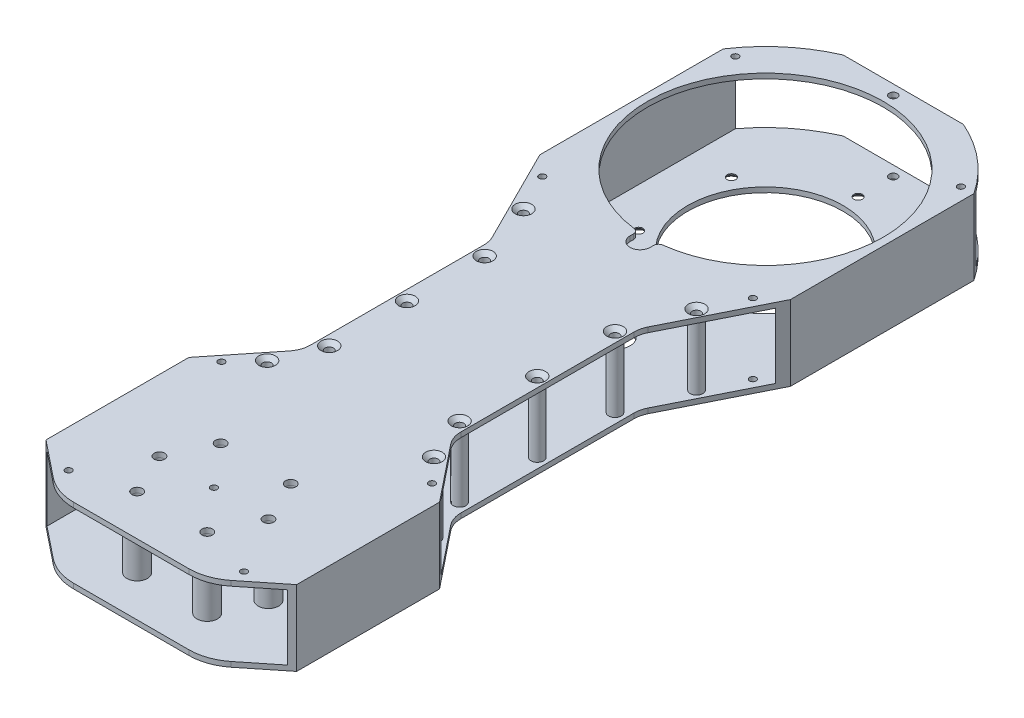
SolidWorks part; units mm, degrees
material "6061-T4 (SS)"
ref_plane "前视基准面" through (0, 0, 0) normal (0, 0, 1) x (1, 0, 0)
ref_plane "上视基准面" through (0, 0, 0) normal (0, 1, 0) x (1, 0, 0)
ref_plane "右视基准面" through (0, 0, 0) normal (1, 0, 0) x (0, 0, -1)
sketch "草图1" plane through (0, 0, 0) normal (0, 0, 1) x (1, 0, 0)
  line L0 (-48, 13) -> (-48, -13)
  line L1 (-50, 15) -> (50, 15)
  line L2 (-50, 15) -> (-50, -15)
  line L3 (-50, -15) -> (50, -15)
  line L4 (50, 15) -> (50, -15)
  line L5 (-50, 15) -> (50, -15) construction
  line L6 (-50, -15) -> (50, 15) construction
  line L7 (-48, -13) -> (48, -13)
  line L8 (48, 13) -> (48, -13)
  line L9 (-48, 13) -> (48, 13)
  point P0 (0, 0)
  dimension "D1" = 100
  dimension "D2" = 30
  dimension "D3" = 2
extrude "凸台-拉伸1" add sketch "草图1" along normal blind 315
sketch "草图2" plane through (0, -15, 0) normal (0, -1, 0) x (1, 0, 0)
  line L1 (-50, 315) -> (50, 315) construction
  circle A0 centre (0, 275) radius 5
  point P5 (0, 315)
  dimension "D1" = 10
  dimension "D2" = 40
extrude "切除-拉伸1" cut sketch "草图2" against normal up to next
sketch "草图3" plane through (0, 15, 0) normal (0, 1, 0) x (1, 0, 0)
  line L0 (50, 0) -> (-50, 0) construction
  circle A0 centre (0, -55) radius 47
  dimension "D1" = 94
  dimension "D2" = 8
extrude "切除-拉伸2" cut sketch "草图3" against normal up to next
sketch "草图8" plane through (0, -15, 0) normal (0, -1, 0) x (1, 0, 0)
  line L0 (0, 275) -> (-18.5467, 297.1031) construction
  line L1 (0, -16.5) -> (0, 16.5) construction
  line L2 (0, 275) -> (18.5467, 297.1031) construction
  line L3 (0, 275) -> (14.5634, 275) construction
  circle A0 centre (0, 275) radius 21.75 construction
  circle A1 centre (-13.9806, 291.6615) radius 2.1
  circle A2 centre (13.9806, 291.6615) radius 2.1
  circle A3 centre (13.9806, 258.3385) radius 2.1
  circle A4 centre (-13.9806, 258.3385) radius 2.1
  circle A5 centre (-21.75, 275) radius 2.1
  circle A6 centre (21.75, 275) radius 2.1
  dimension "D1" = 43.5
  dimension "D3" = 4.2
  dimension "D2" = 80
extrude "切除-拉伸7" cut sketch "草图8" against normal through all
sketch "草图9" plane through (0, -15, 0) normal (0, -1, 0) x (1, 0, 0)
  circle A0 centre (0, 55) radius 37 construction
  circle A1 centre (0, 55) radius 47 construction
  circle A2 centre (-32.0429, 73.5) radius 1.6
  circle A3 centre (0, 92) radius 1.6
  circle A4 centre (32.0429, 73.5) radius 1.6
  circle A5 centre (32.0429, 36.5) radius 1.6
  circle A6 centre (0, 18) radius 1.6
  circle A7 centre (-32.0429, 36.5) radius 1.6
  point P18 (0, 55)
  dimension "D1" = 74
  dimension "D2" = 3.2
  dimension "D3" = 6
extrude "切除-拉伸8" cut sketch "草图9" against normal up to next
sketch "草图5" plane through (0, 15, 0) normal (0, 1, 0) x (1, 0, 0)
  line L0 (-50, -95) -> (-30, -135)
  line L1 (-50, -315) -> (-50, 0) construction
  line L2 (-30, -135) -> (-30, -210)
  line L3 (-30, -210) -> (-50, -235)
  line L4 (-50, -95) -> (-50, -235)
  line L5 (0, -16.5) -> (0, 16.5) construction
  line L6 (50, -95) -> (50, -235)
  line L7 (30, -210) -> (50, -235)
  line L8 (30, -135) -> (30, -210)
  line L9 (50, -95) -> (30, -135)
  line L10 (50, 0) -> (-50, 0) construction
  line L11 (50, -315) -> (-50, -315) construction
  dimension "D1" = 20
  dimension "D2" = 25
  dimension "D3" = 40
  dimension "D4" = 95
  dimension "D5" = 80
extrude "切除-拉伸4" cut sketch "草图5" against normal through all
sketch "草图6" plane through (0, 15, 0) normal (0, 1, 0) x (1, 0, 0)
  line L1 (-23.9792, 0) -> (-50, 0)
  line L3 (-50, -95) -> (-50, 0) construction
  line L9 (50, 0) -> (-50, 0) construction
  line L10 (50, 0) -> (23.9792, 0)
  line L13 (50, -95) -> (50, 0) construction
  line L14 (50, -95) -> (50, -88.9217)
  line L15 (-50, -21.8338) -> (-50, 0)
  line L16 (50, -21.8338) -> (50, 0)
  arc A0 (50, -21.8338) -> (23.9792, 0) centre (0, -55) ccw
  arc A1 (-23.9792, 0) -> (-50, -21.8338) centre (0, -55) ccw
  line M11 (-50, 0) -> (-50, -95)
  line M23 (50, -95) -> (50, 0)
  line M24 (50, 0) -> (-50, 0)
  dimension "D1" = 60
extrude "切除-拉伸5" cut sketch "草图6" against normal through all contours A1 M24 M11 | A0 M23 M24 region at (-42.232, 15, 6.5725) region at (42.232, 15, 6.5725)
fillet "圆角1" radius 10 8 edges at (-30, 14, 210) (-30, -14, 210) (-30, -14, 135) (-30, 14, 135) (30, 14, 210) (30, -14, 210) (30, 14, 135) (30, -14, 135)
sketch "草图10" plane through (0, 15, 0) normal (0, 1, 0) x (1, 0, 0)
  line L0 (-30, -206.4922) -> (-30, -137.3607) construction
  line L1 (0, -16.5) -> (0, 16.5) construction
  line L2 (-26, -141) -> (-26, -203) construction
  line L3 (-31.0557, -132.8885) -> (-50, -95) construction
  line L4 (-50, -235) -> (-32.1913, -212.7391) construction
  circle A0 centre (-26, -141) radius 1.6
  circle A1 centre (0, -55) radius 47 construction
  circle A2 centre (-26, -203) radius 1.6
  circle A3 centre (0, -275) radius 5 construction
  circle A4 centre (26, -203) radius 1.6
  circle A5 centre (26, -141) radius 1.6
  circle A6 centre (-26, -172) radius 1.6
  circle A7 centre (26, -172) radius 1.6
  circle A8 centre (-34.5279, -117) radius 1.6
  circle A9 centre (-33.2775, -220.5) radius 1.6
  circle A10 centre (33.2775, -220.5) radius 1.6
  circle A11 centre (34.5279, -117) radius 1.6
  dimension "D1" = 3.2
  dimension "D4" = 72
  dimension "D5" = 4
  dimension "D2" = 4
  dimension "D3" = 86
  dimension "D6" = 18
  dimension "D7" = 4
  dimension "D8" = 12
extrude "切除-拉伸9" cut sketch "草图10" against normal through all
sketch "草图11" plane through (0, -13, 0) normal (0, 1, 0) x (1, 0, 0)
  line L0 (0, -16.5) -> (0, 16.5) construction
  circle A0 centre (-26, -141) radius 2.5
  circle A1 centre (-26, -203) radius 2.5
  circle A2 centre (26, -203) radius 2.5
  circle A3 centre (26, -141) radius 2.5
  circle A4 centre (-26, -172) radius 2.5
  circle A5 centre (26, -172) radius 2.5
  circle A6 centre (-33.2775, -220.5) radius 2.5
  circle A7 centre (33.2775, -220.5) radius 2.5
  circle A8 centre (-34.5279, -117) radius 2.5
  circle A9 centre (34.5279, -117) radius 2.5
  dimension "D1" = 5
extrude "凸台-拉伸2" add sketch "草图11" along normal up to surface (26 mm away) up to face at (33.2775, 13, 218.9)
sketch "草图13" plane through (0, -15, 0) normal (0, -1, 0) x (1, 0, 0)
  circle A0 centre (0, 55) radius 31
  circle A2 centre (0, 55) radius 47 construction
  dimension "D1" = 62
extrude "切除-拉伸11" cut sketch "草图13" against normal through all
hole_wizard "M3 十字槽沉头木螺钉的锥形沉头孔1" positions "3D草图1" profile "草图14" countersink size "M3" standard "GB"
sketch3d "3D草图1"
  circle A0 centre (-32.0429, -15, 73.5) radius 1.6 construction
  circle A1 centre (0, -15, 92) radius 1.6 construction
  circle A2 centre (32.0429, -15, 73.5) radius 1.6 construction
  circle A3 centre (32.0429, -15, 36.5) radius 1.6 construction
  circle A4 centre (0, -15, 18) radius 1.6 construction
  circle A5 centre (-32.0429, -15, 36.5) radius 1.6 construction
  point P0 (0, -15, 92)
  point P2 (32.0429, -15, 73.5)
  point P4 (32.0429, -15, 36.5)
  point P6 (0, -15, 18)
  point P8 (-32.0429, -15, 36.5)
  point P10 (-32.0429, -15, 73.5)
  point P15 (-32.0429, -16.6, 73.5)
  point P19 (0, -16.6, 92)
  point P23 (32.0429, -16.6, 73.5)
  point P27 (32.0429, -16.6, 36.5)
  point P31 (0, -16.6, 18)
  point P34 (-32.0429, -16.6, 36.5)
sketch "草图14" plane through (0, -15, 92) normal (1, 0, 0) x (0, 0, -1)
  line L0 (0, 0) -> (0, 8.5215)
  line L1 (0, 8.5215) -> (1.7, 7.5)
  line L2 (1.7, 7.5) -> (1.7, 1.6)
  line L3 (1.7, 1.6) -> (3.3, 0)
  line L5 (3.3, 0) -> (0, 0)
  line L6 (-1.7, 1.6) -> (-3.3, 0) construction
  line L10 (0, 8.5215) -> (-1.7, 7.5) construction
  line L11 (0, -6.35) -> (0, 107.95) construction
  dimension "孔直径" = 3.4
  dimension "孔深度" = 7.5
  dimension "近端锥形沉头孔直径" = 6.6
  dimension "近端锥形沉头孔角度" = 90
  dimension "导头角度" = 118
sketch "草图16" plane through (0, -15, 0) normal (0, -1, 0) x (1, 0, 0)
  line L0 (0, -16.5) -> (0, 16.5) construction
  circle A0 centre (0, 115) radius 6
  circle A1 centre (0, 55) radius 31 construction
  dimension "D1" = 12
  dimension "D2" = 60
extrude "切除-拉伸12" cut sketch "草图16" against normal up to surface (2 mm away) up to face at (0, -13, 93.7)
sketch "草图17" plane through (0, 15, 0) normal (0, 1, 0) x (1, 0, 0)
  line L0 (0, -16.5) -> (0, 16.5) construction
  line L1 (-4, -105) -> (-4, -101.8295)
  line L2 (4, -105) -> (4, -101.8295)
  arc A0 (-4, -105) -> (4, -105) centre (0, -105) ccw
  circle A1 centre (0, -55) radius 47 construction
  arc A2 (-4, -101.8295) -> (4, -101.8295) centre (0, -55) ccw
  dimension "D1" = 50
  dimension "D2" = 8
extrude "切除-拉伸13" cut sketch "草图17" against normal up to surface (2 mm away) up to face at (34.5279, 13, 114.5)
fillet "圆角2" radius 2 2 edges at (4, 14, 101.8295) (-4, 14, 101.8295)
ref_axis "基准轴1" through (0, 0, 0) along (0, 0, -1)
sketch "草图19" plane through (0, 15, 0) normal (0, 1, 0) x (1, 0, 0)
  line L0 (-48, -99) -> (-48, -19) construction
  line L1 (0, -16.5) -> (0, 16.5) construction
  circle A0 centre (-42, -102) radius 1.3
  circle A1 centre (-42, -230) radius 1.3
  circle A2 centre (0, -55) radius 31 construction
  circle A3 centre (42, -230) radius 1.3
  circle A4 centre (42, -102) radius 1.3
  dimension "D1" = 2.6
  dimension "D2" = 6
  dimension "D3" = 47
  dimension "D4" = 128
extrude "切除-拉伸15" cut sketch "草图19" against normal through all
sketch "草图20" plane through (0, 15, 0) normal (0, 1, 0) x (1, 0, 0)
  line L0 (-20.0283, -224.6757) -> (0.0451, -213.62)
  line L1 (-20.0283, -224.6757) -> (-0.0451, -255.7683)
  line L2 (-36.1251, -231.4671) -> (-40.6769, -242.8464)
  line L3 (-40.6769, -242.8464) -> (-38.401, -272.9275)
  line L4 (-38.401, -272.9275) -> (-15.0486, -267.0894)
  line L5 (-15.0486, -267.0894) -> (-36.1251, -231.4671)
  line L6 (0.0081, -277.5729) -> (-13.6536, -285.6561)
  line L7 (-13.6536, -285.6561) -> (-0.0081, -296.1926)
  line L11 (0, -16.5) -> (0, 16.5) construction
  line L12 (13.6536, -285.6561) -> (-0.0081, -296.1926)
  line L13 (0.0081, -277.5729) -> (13.6536, -285.6561)
  line L14 (38.401, -272.9275) -> (15.0486, -267.0894)
  line L15 (40.6769, -242.8464) -> (38.401, -272.9275)
  line L16 (36.1251, -231.4671) -> (40.6769, -242.8464)
  line L17 (15.0486, -267.0894) -> (36.1251, -231.4671)
  line L18 (20.0283, -224.6757) -> (-0.0451, -255.7683)
  line L19 (20.0283, -224.6757) -> (0.0451, -213.62)
  line L25 (-21.8239, -199.6757) -> (-18.2763, -197.7345)
  line L26 (-18.2763, -197.7345) -> (-16.1091, -203.3665)
  line L27 (-16.1091, -203.3665) -> (-17.6821, -205.1142)
  line L28 (-17.6821, -205.1142) -> (-18.8118, -206.3694)
  line L29 (-18.8118, -206.3694) -> (-21.0207, -206.3694)
  line L30 (-21.0207, -206.3694) -> (-21.8239, -199.6757)
  line L31 (0.0451, -118.8015) -> (-15.0486, -136.7959)
  line L32 (-15.0486, -136.7959) -> (0.0451, -152.5667)
  line L33 (0.0451, -152.5667) -> (16.1914, -137.1137)
  line L34 (16.1914, -137.1137) -> (0.0451, -118.8015)
  line L36 (18.8118, -206.3694) -> (21.0207, -206.3694)
  line L37 (17.6821, -205.1142) -> (18.8118, -206.3694)
  line L38 (16.1091, -203.3665) -> (17.6821, -205.1142)
  line L39 (18.2763, -197.7345) -> (16.1091, -203.3665)
  line L40 (21.8239, -199.6757) -> (18.2763, -197.7345)
  line L41 (21.0207, -206.3694) -> (21.8239, -199.6757)
extrude "切除-拉伸16" [suppressed] cut sketch "草图20" against normal up to next
sketch "草图21" plane through (-50, 0, 0) normal (-1, 0, 0) x (0, 0, 1)
  line L0 (244.292, 11.5227) -> (256.5602, 13)
  line L1 (256.5602, 13) -> (276.1507, 13)
  line L2 (276.1507, 13) -> (282.895, 0.9245)
  line L3 (282.895, 0.9245) -> (265.681, 0.9245)
  line L4 (265.681, 0.9245) -> (250.4261, -2.4155)
  line L5 (250.4261, -2.4155) -> (242.9432, 7.0907)
  line L6 (242.9432, 7.0907) -> (244.292, 11.5227)
  line L7 (315, 15) -> (235, 15) construction
  dimension "D1" = 2
extrude "切除-拉伸17" [suppressed] cut sketch "草图21" against normal through all
fillet "圆角4" [suppressed] radius 2
sketch "草图22" plane through (0, -15, 0) normal (0, -1, 0) x (1, 0, 0)
  line L0 (-50, 292) -> (-30, 308)
  line L1 (-50, 315) -> (-50, 235) construction
  line L2 (-30, 308) -> (30, 308)
  line L3 (30, 308) -> (50, 292)
  line L4 (50, 315) -> (50, 235) construction
  line L5 (50, 292) -> (50, 315)
  line L6 (50, 315) -> (-50, 315)
  line L7 (-50, 315) -> (-50, 292)
  point P12 (0, 315)
  point P13 (0, 308)
  dimension "D1" = 7
  dimension "D2" = 20
  dimension "D3" = 16
extrude "切除-拉伸18" cut sketch "草图22" against normal through all
fillet "圆角5" radius 20 4 edges at (-30, 14, 308) (30, 14, 308) (30, -14, 308) (-30, -14, 308)
hole_wizard "M3 十字槽沉头木螺钉的锥形沉头孔2" positions "3D草图2" profile "草图23" countersink size "M3" standard "GB" end condition up to next
sketch3d "3D草图2"
  line L0 (-33.2775, -15, 220.5) -> (-33.2775, -13, 220.5) construction
  line L1 (-26, -15, 203) -> (-26, -13, 203) construction
  line L4 (-34.5279, -15, 117) -> (-34.5279, -13, 117) construction
  line L8 (33.2775, -15, 220.5) -> (33.2775, -13, 220.5) construction
  circle A0 centre (34.5279, -15, 117) radius 1.6 construction
  circle A1 centre (26, -15, 141) radius 1.6 construction
  circle A2 centre (26, -15, 172) radius 1.6 construction
  circle A3 centre (26, -15, 203) radius 1.6 construction
  circle A4 centre (-26, -15, 172) radius 1.6 construction
  circle A5 centre (-26, -15, 141) radius 1.6 construction
  point P0 (-33.2775, -15, 220.5)
  point P4 (-26, -15, 203)
  point P16 (-34.5279, -15, 117)
  point P32 (33.2775, -15, 220.5)
  point P41 (34.5279, -15, 117)
  point P43 (26, -15, 141)
  point P45 (26, -15, 172)
  point P47 (26, -15, 203)
  point P49 (-26, -15, 172)
  point P51 (-26, -15, 141)
  point P56 (34.5279, -13.4, 117)
  point P60 (26, -13.4, 141)
  point P63 (26, -13.4, 172)
  point P66 (26, -13.4, 203)
  point P70 (-26, -13.4, 172)
  point P75 (-26, -13.4, 141)
sketch "草图23" plane through (-33.2775, -15, 220.5) normal (1, 0, 0) x (0, 0, -1)
  line L0 (0, 0) -> (0, 28)
  line L1 (0, 28) -> (1.7, 28)
  line L2 (1.7, 28) -> (1.7, 1.6)
  line L3 (1.7, 1.6) -> (3.3, 0)
  line L5 (3.3, 0) -> (0, 0)
  line L6 (-1.7, 1.6) -> (-3.3, 0) construction
  line L11 (0, -6.35) -> (0, 107.95) construction
  dimension "通孔孔直径" = 3.4
  dimension "通孔孔深度" = 28
  dimension "近端锥形沉头孔直径" = 6.6
  dimension "近端锥形沉头孔角度" = 90
sketch "草图24" plane through (0, 15, 0) normal (0, 1, 0) x (1, 0, 0)
  line L0 (0, -16.5) -> (0, 16.5) construction
  line L1 (23.9792, 0) -> (-23.9792, 0) construction
  line L2 (-48, -99) -> (-48, -19) construction
  circle A0 centre (-45, -22) radius 1.3
  circle A1 centre (45, -22) radius 1.3
  dimension "D1" = 2.6
  dimension "D2" = 3
  dimension "D3" = 22
extrude "切除-拉伸19" cut sketch "草图24" against normal blind 10
hole_wizard "M3 十字槽沉头木螺钉的锥形沉头孔3" positions "草图25" profile "草图26" countersink size "M3" standard "GB"
sketch "草图25" plane through (0, 15, 0) normal (0, 1, 0) x (1, 0, 0)
  circle A0 centre (-34.5279, -117) radius 1.7 construction
  circle A1 centre (-26, -141) radius 1.7 construction
  circle A2 centre (-26, -172) radius 1.7 construction
  circle A3 centre (-26, -203) radius 1.7 construction
  circle A4 centre (-33.2775, -220.5) radius 1.7 construction
  circle A5 centre (33.2775, -220.5) radius 1.7 construction
  circle A6 centre (26, -203) radius 1.7 construction
  circle A7 centre (26, -172) radius 1.7 construction
  circle A8 centre (26, -141) radius 1.7 construction
  circle A9 centre (34.5279, -117) radius 1.7 construction
  point P0 (-34.5279, -117)
  point P3 (-26, -141)
  point P6 (-26, -172)
  point P9 (-26, -203)
  point P12 (-33.2775, -220.5)
  point P15 (33.2775, -220.5)
  point P18 (26, -203)
  point P21 (26, -172)
  point P24 (26, -141)
  point P27 (34.5279, -117)
sketch "草图26" plane through (-34.5279, 15, 117) normal (1, 0, 0) x (0, 0, 1)
  line L0 (0, 0) -> (0, 8.5215)
  line L1 (0, 8.5215) -> (1.7, 7.5)
  line L2 (1.7, 7.5) -> (1.7, 1.6)
  line L3 (1.7, 1.6) -> (3.3, 0)
  line L5 (3.3, 0) -> (0, 0)
  line L6 (-1.7, 1.6) -> (-3.3, 0) construction
  line L10 (0, 8.5215) -> (-1.7, 7.5) construction
  line L11 (0, -6.35) -> (0, 107.95) construction
  dimension "孔直径" = 3.4
  dimension "孔深度" = 7.5
  dimension "近端锥形沉头孔直径" = 6.6
  dimension "近端锥形沉头孔角度" = 90
  dimension "导头角度" = 118
sketch "草图27" plane through (0, -13, 0) normal (0, 1, 0) x (1, 0, 0)
  circle A0 centre (-13.9806, -258.3385) radius 2.2
  circle A1 centre (13.9806, -258.3385) radius 2.2
  circle A2 centre (21.75, -275) radius 2.2
  circle A3 centre (13.9806, -291.6615) radius 2.2
  circle A4 centre (-13.9806, -291.6615) radius 2.2
  circle A5 centre (-21.75, -275) radius 2.2
  circle A6 centre (-13.9806, -258.3385) radius 4.1
  circle A7 centre (13.9806, -258.3385) radius 4.1
  circle A8 centre (21.75, -275) radius 4.1
  circle A9 centre (13.9806, -291.6615) radius 4.1
  circle A10 centre (-13.9806, -291.6615) radius 4.1
  circle A11 centre (-21.75, -275) radius 4.1
  dimension "D1" = 4.4
  dimension "D2" = 8.2
extrude "凸台-拉伸3" add sketch "草图27" along normal up to surface (26 mm away) up to face at (-45, 13, 20.7)
sketch "草图28" plane through (0, 15, 0) normal (0, 1, 0) x (1, 0, 0)
  line L0 (0, -16.5) -> (0, 16.5) construction
  line L1 (-22.9844, -308) -> (22.9844, -308) construction
  circle A0 centre (-35, -298) radius 1.3
  circle A1 centre (35, -298) radius 1.3
  circle A2 centre (0, -275) radius 1.3
  point P2 (0, -275)
  dimension "D1" = 2.6
  dimension "D2" = 70
  dimension "D3" = 10
extrude "切除-拉伸20" cut sketch "草图28" against normal blind 2
sketch "草图31" plane through (0, 15, 0) normal (0, 1, 0) x (1, 0, 0)
  line L0 (0, 0) -> (0, 15.84) construction
  line L1 (23.9792, 0) -> (-23.9792, 0) construction
  circle A0 centre (0, -4) radius 1.65
  dimension "D1" = 3.3
  dimension "D2" = 4
extrude "切除-拉伸21" cut sketch "草图31" against normal through all
